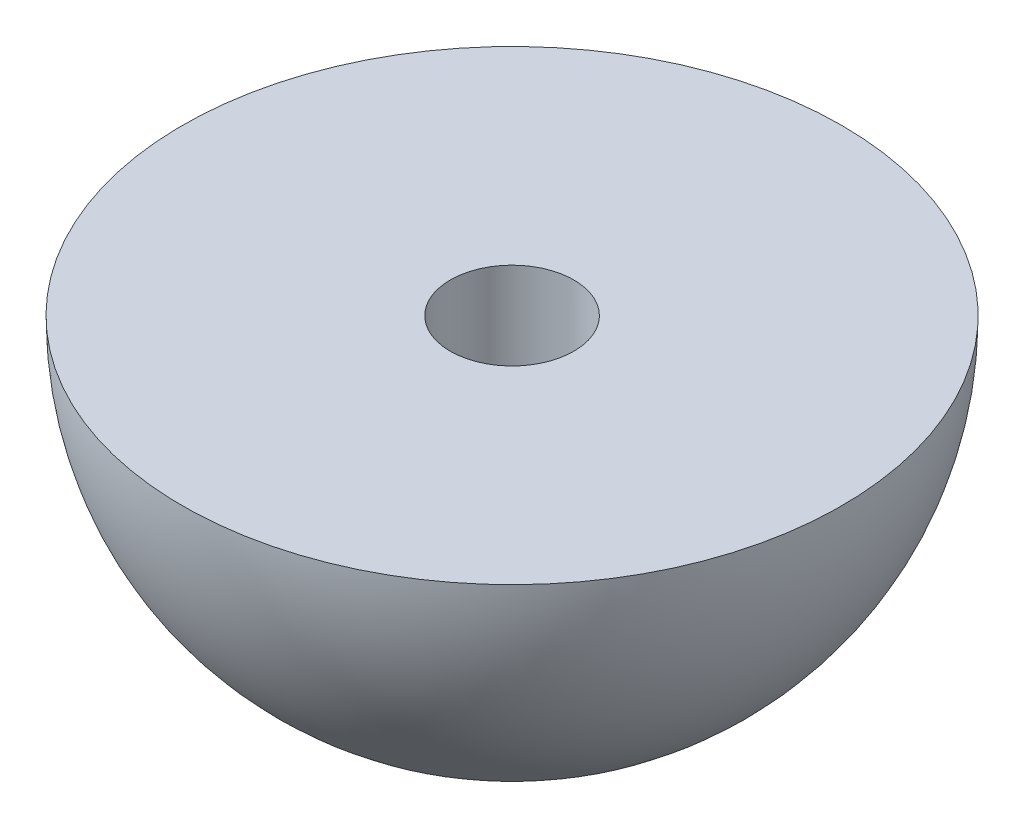
SolidWorks part; units mm, degrees
ref_plane "正面" through (0, 0, 0) normal (0, 0, 1) x (1, 0, 0)
ref_plane "平面" through (0, 0, 0) normal (0, 1, 0) x (1, 0, 0)
ref_plane "右側面" through (0, 0, 0) normal (1, 0, 0) x (0, 0, -1)
sketch "ｽｹｯﾁ1" plane through (0, 0, 0) normal (0, 0, 1) x (1, 0, 0)
  line L0 (0, -8) -> (0, 0)
  line L1 (0, 0) -> (8, 0)
  arc A0 (8, 0) -> (0, -8) centre (0, 0) cw
revolve "回転1" add sketch "ｽｹｯﾁ1" angle 360 about L0
sketch "ｽｹｯﾁ2" plane through (0, 0, 0) normal (0, 1, 0) x (1, 0, 0)
  circle A0 centre (0, 0) radius 1.5
extrude "ｶｯﾄ - 押し出し1" cut sketch "ｽｹｯﾁ2" against normal through all
